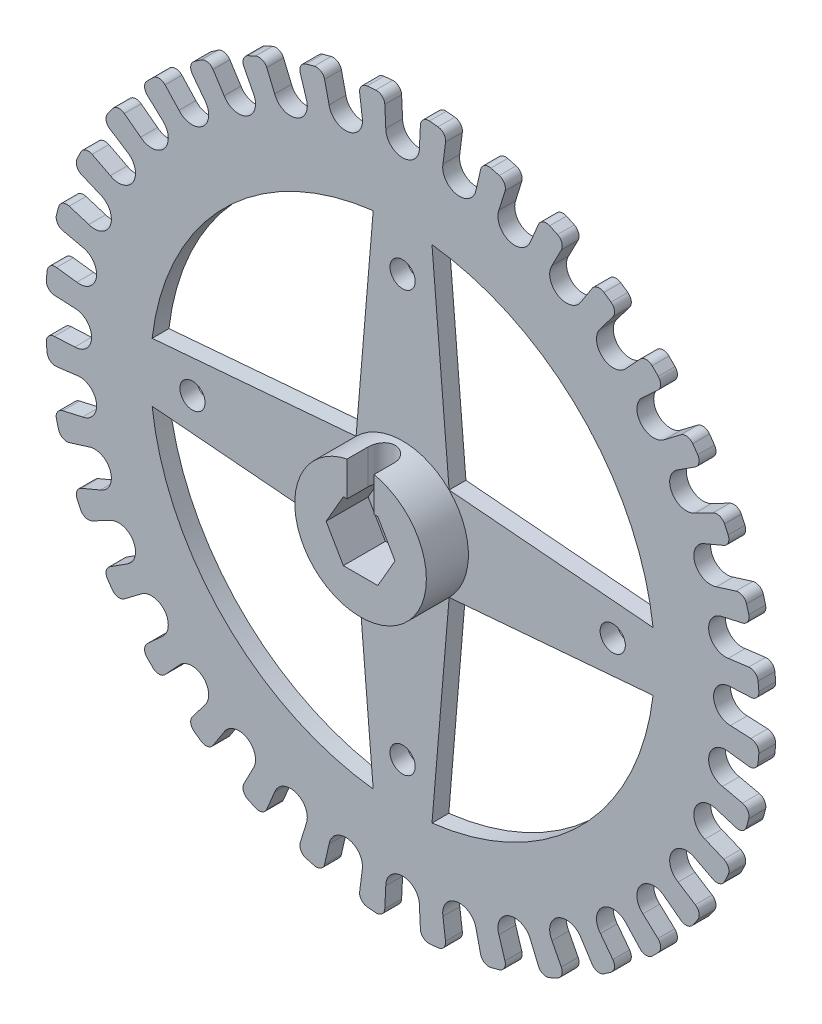
SolidWorks part; units mm, degrees
ref_plane "Front Plane" through (0, 0, 0) normal (0, 0, 1) x (1, 0, 0)
ref_plane "Top Plane" through (0, 0, 0) normal (0, 1, 0) x (1, 0, 0)
ref_plane "Right Plane" through (0, 0, 0) normal (1, 0, 0) x (0, 0, -1)
sketch "Sketch1" plane through (0, 0, 0) normal (0, 0, 1) x (1, 0, 0)
  line L0 (0, 0) -> (0, 6) construction
  line L1 (0, 25) -> (1.65, 25) construction
  line L2 (-1.65, 27.0934) -> (1.65, 27.0934) construction
  line L3 (-1.65, 27.0934) -> (-1.65, 38.3614) construction
  line L4 (-1.65, 38.3614) -> (1.65, 38.3614) construction
  line L5 (1.65, 27.0934) -> (1.65, 38.3614) construction
  line L6 (-3.4971, 29.7955) -> (-5.535, 5.535)
  line L7 (1.5588, 0) -> (0.7794, 1.35)
  line L8 (0.7794, 1.35) -> (-0.7794, 1.35)
  line L9 (-0.7794, 1.35) -> (-1.5588, 0)
  line L10 (-1.5588, 0) -> (-0.7794, -1.35)
  line L11 (-0.7794, -1.35) -> (0.7794, -1.35)
  line L12 (0.7794, -1.35) -> (1.5588, 0)
  line L13 (3.4971, 29.7955) -> (5.535, 5.535)
  line L14 (29.7955, 3.4971) -> (5.535, 5.535)
  line L15 (29.7955, -3.4971) -> (5.535, -5.535)
  line L16 (3.4971, -29.7955) -> (5.535, -5.535)
  line L17 (-3.4971, -29.7955) -> (-5.535, -5.535)
  line L18 (-29.7955, -3.4971) -> (-5.535, -5.535)
  line L19 (-29.7955, 3.4971) -> (-5.535, 5.535)
  line L20 (3.8999, 25) -> (12.5438, 25) construction
  line L27 (0, 23.5) -> (0, 76.7228) construction
  circle A0 centre (0, 0) radius 42.5
  circle A2 centre (0, 25) radius 1.5
  arc A3 (-3.4971, 29.7955) -> (-29.7955, 3.4971) centre (0, 0) ccw
  circle A4 centre (0, 0) radius 1.35 construction
  circle A5 centre (25, 0) radius 1.5
  circle A6 centre (0, -25) radius 1.5
  circle A7 centre (-25, 0) radius 1.5
  arc A8 (-29.7955, -3.4971) -> (-3.4971, -29.7955) centre (0, 0) ccw
  arc A9 (3.4971, -29.7955) -> (29.7955, -3.4971) centre (0, 0) ccw
  arc A10 (29.7955, 3.4971) -> (3.4971, 29.7955) centre (0, 0) ccw
  point P7 (0, 42.5)
  point P10 (0, 38.3614)
  dimension "D1" = 85
  dimension "D2" = 25
  dimension "D3" = 3
  dimension "D6" = 2.7
  dimension "D4" = 3.3
  dimension "D5" = 0
  dimension "D8" = 4
extrude "Boss-Extrude1" add sketch "Sketch1" along normal blind 2
sketch "Sketch2" plane through (0, 0, 2) normal (0, 0, 1) x (1, 0, 0)
  line L0 (0, 0) -> (0, 46.0615) construction
  line L1 (-2, 39) -> (-2.25, 44.1517)
  line L2 (-2.25, 44.1517) -> (2.25, 44.1517)
  line L3 (2.25, 44.1517) -> (2, 39)
  arc A0 (-2, 39) -> (2, 39) centre (0, 39) ccw
  circle A1 centre (0, 0) radius 42.5 construction
  point P4 (0, 44.1517)
  point P5 (0, 42.5)
  dimension "D1" = 3.5
  dimension "D3" = 2.25
  dimension "D2" = 2
extrude "Cut-Extrude1" cut sketch "Sketch2" against normal through all
sketch "Sketch5" plane through (0, 0, 2) normal (0, 0, 1) x (1, 0, 0)
  line L0 (3.8898, 40.5) -> (-1.3229, 40.5) construction
  line L1 (0, 42.5) -> (3.8939, 42.5) construction
  line L4 (-2, 39) -> (-2.1672, 42.4447)
  line L5 (-2, 39) -> (-2.1672, 42.4447)
  line L6 (2.1672, 42.4447) -> (2, 39)
  line L7 (2.1672, 42.4447) -> (2, 39)
  circle A0 centre (0, 39) radius 2 construction
  circle A1 centre (0, 0) radius 42.5 construction
  arc A3 (-2.1672, 42.4447) -> (2.1672, 42.4447) centre (0, 0) ccw
  arc A4 (-2.1672, 42.4447) -> (2.1672, 42.4447) centre (0, 0) ccw
  arc A194 (-2, 39) -> (2, 39) centre (0, 39) ccw
  arc A195 (-2, 39) -> (2, 39) centre (0, 39) ccw
  dimension "D1" = 0
  dimension "D2" = 2
fillet "Fillet1" radius 1 2 edges at (-2.1672, 42.4447, 1) (2.1672, 42.4447, 1)
pattern_circular "CirPattern1" count 36 over 360 about axis through (0, 0, 2) along (0, 0, -1) of "Fillet1", "Cut-Extrude1" reverse direction yes
sketch "Sketch6" plane through (0, 0, 2) normal (0, 0, 1) x (1, 0, 0)
  circle A0 centre (0, 0) radius 7.8277
extrude "Boss-Extrude2" add sketch "Sketch6" along normal blind 5
sketch "Sketch7" plane through (0, 0, 7) normal (0, 0, 1) x (1, 0, 0)
  line L1 (4.0992, 0) -> (2.0496, 3.55)
  line L2 (2.0496, 3.55) -> (-2.0496, 3.55)
  line L3 (-2.0496, 3.55) -> (-4.0992, 0)
  line L4 (-4.0992, 0) -> (-2.0496, -3.55)
  line L5 (-2.0496, -3.55) -> (2.0496, -3.55)
  line L6 (2.0496, -3.55) -> (4.0992, 0)
  circle A0 centre (0, 0) radius 3.55 construction
  dimension "D1" = 7.1
extrude "Cut-Extrude2" cut sketch "Sketch7" against normal blind 5
sketch "Sketch8" plane through (0, 3.55, 0) normal (0, -1, 0) x (1, 0, 0)
  line L2 (1.6, 4.5) -> (1.6, 7.9519)
  line L3 (1.6, 7.9519) -> (-1.6, 7.9519)
  line L4 (-1.6, 4.5) -> (-1.6, 7.9519)
  arc A0 (-1.6, 4.5) -> (1.6, 4.5) centre (0, 4.5) ccw
extrude "Cut-Extrude3" cut sketch "Sketch8" against normal blind 5
